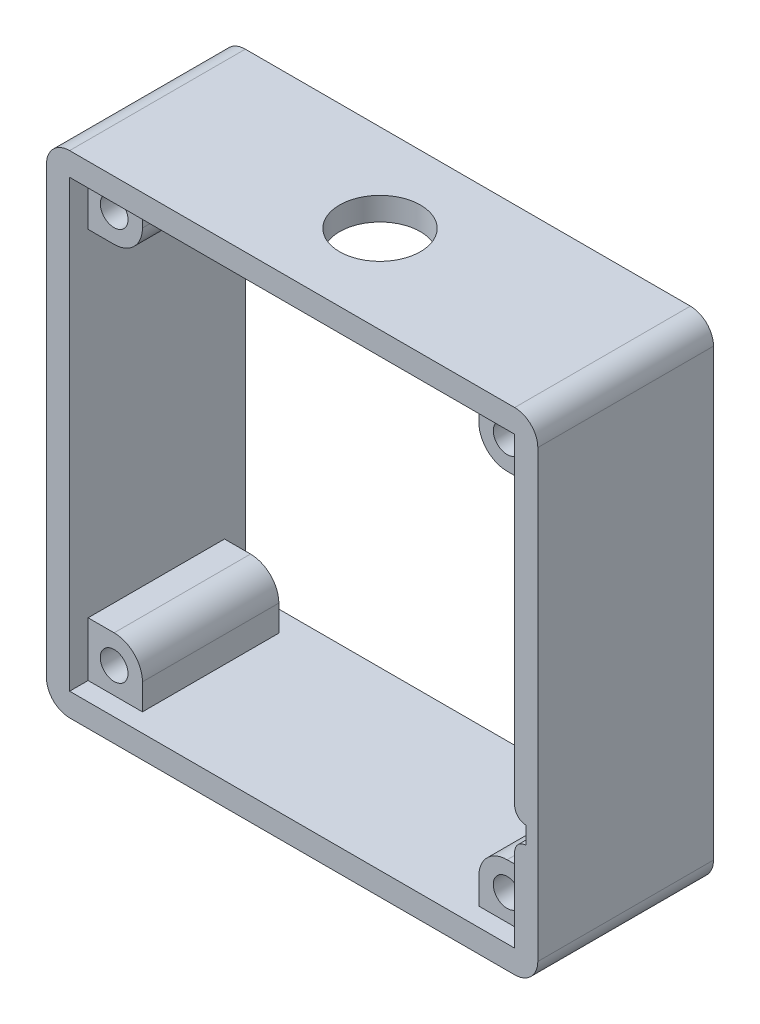
SolidWorks part; units mm, degrees
ref_plane "Front Plane" through (0, 0, 0) normal (0, 0, 1) x (1, 0, 0)
ref_plane "Top Plane" through (0, 0, 0) normal (0, 1, 0) x (1, 0, 0)
ref_plane "Right Plane" through (0, 0, 0) normal (1, 0, 0) x (0, 0, -1)
sketch "Sketch1" plane through (0, 0, 0) normal (0, 0, 1) x (1, 0, 0)
  line L0 (19.05, -19.05) -> (19.05, 19.05) construction
  line L5 (21.25, 21.25) -> (-21.25, 21.25)
  line L6 (-21.25, 21.25) -> (-21.25, -21.25)
  line L7 (-19.05, -19.05) -> (19.05, -19.05) construction
  line L8 (-19.05, 19.05) -> (-19.05, -19.05) construction
  line L9 (19.05, 19.05) -> (-19.05, 19.05) construction
  line L10 (19.05, -19.05) -> (19.05, 19.05) construction
  line L11 (-19.05, -19.05) -> (19.05, -19.05) construction
  line L12 (-19.05, 19.05) -> (-19.05, -19.05) construction
  line L13 (19.05, 19.05) -> (-19.05, 19.05) construction
  line L14 (19.25, -19.25) -> (19.25, 19.25)
  line L15 (19.25, 19.25) -> (-19.25, 19.25)
  line L16 (-19.25, 19.25) -> (-19.25, -19.25)
  line L17 (-19.25, -19.25) -> (19.25, -19.25)
  line L18 (-21.25, -21.25) -> (21.25, -21.25)
  line L19 (21.25, -21.25) -> (21.25, 21.25)
  point P336 (-1.13, 0.5101)
  dimension "D2" = 2
  dimension "D1" = 0.2
extrude "Boss-Extrude2" add sketch "Sketch1" against normal up to surface (15.2 mm away)
sketch "Sketch2" plane through (0, 0, -1.6) normal (0, 0, -1) x (-1, 0, 0)
  line L0 (17, -14.55) -> (19.25, -14.55)
  line L1 (19.25, 19.25) -> (19.25, -19.25) construction
  line L2 (14.55, -17) -> (14.55, -19.25)
  line L3 (19.25, -19.25) -> (-19.25, -19.25) construction
  line L4 (19.25, -19.25) -> (14.55, -19.25)
  line L5 (19.25, -14.55) -> (19.25, -19.25)
  line L6 (19.05, -19.05) -> (-19.05, -19.05) construction
  line L7 (0, 0) -> (-50000, 0) construction
  line L8 (0, 0) -> (0, 50000) construction
  line L9 (19.25, 14.55) -> (19.25, 19.25)
  line L10 (19.25, 19.25) -> (14.55, 19.25)
  line L11 (14.55, 17) -> (14.55, 19.25)
  line L12 (17, 14.55) -> (19.25, 14.55)
  line L13 (-19.25, -14.55) -> (-19.25, -19.25)
  line L14 (-19.25, -19.25) -> (-14.55, -19.25)
  line L15 (-14.55, -17) -> (-14.55, -19.25)
  line L16 (-17, -14.55) -> (-19.25, -14.55)
  line L17 (-17, 14.55) -> (-19.25, 14.55)
  line L18 (-14.55, 17) -> (-14.55, 19.25)
  line L19 (-19.25, 19.25) -> (-14.55, 19.25)
  line L20 (-19.25, 14.55) -> (-19.25, 19.25)
  circle A2 centre (17, -17) radius 1.2 construction
  circle A3 centre (17, -17) radius 1.2
  arc A4 (17, -14.55) -> (14.55, -17) centre (17, -17) ccw
  arc A5 (17, 14.55) -> (14.55, 17) centre (17, 17) cw
  circle A6 centre (17, 17) radius 1.2
  arc A7 (-17, -14.55) -> (-14.55, -17) centre (-17, -17) cw
  circle A8 centre (-17, -17) radius 1.2
  circle A9 centre (-17, 17) radius 1.2
  arc A10 (-17, 14.55) -> (-14.55, 17) centre (-17, 17) ccw
  dimension "D1" = 4.5
extrude "Boss-Extrude4" add sketch "Sketch2" along normal offset from surface (11.8 mm away) 0.2 up to face at (0, 0, 0)
fillet "Fillet1" radius 2 4 edges at (-21.25, 21.25, -7.6) (21.25, 21.25, -7.6) (21.25, -21.25, -7.6) (-21.25, -21.25, -7.6)
sketch "Sketch3" plane through (0, 0, 0) normal (0, 0, 1) x (1, 0, 0)
  line L0 (20.25, -11.05) -> (20.25, -9.55) construction
  line L1 (20.25, -11.05) -> (20.25, -9.55)
  line L2 (19.25, -8.55) -> (19.25, -12.05)
  arc A0 (19.25, -8.55) -> (20.25, -9.55) centre (20.25, -8.55) ccw construction
  arc A1 (20.25, -11.05) -> (19.25, -12.05) centre (20.25, -12.05) ccw construction
  arc A2 (19.25, -8.55) -> (20.25, -9.55) centre (20.25, -8.55) ccw
  arc A3 (20.25, -11.05) -> (19.25, -12.05) centre (20.25, -12.05) ccw
extrude "Cut-Extrude2" cut sketch "Sketch3" against normal blind 4
sketch "Sketch4" plane through (0, 21.25, 0) normal (0, 1, 0) x (1, 0, 0)
  line L0 (-19.25, 15.2) -> (-19.25, 0) construction
  line L1 (19.25, 0) -> (-19.25, 0) construction
  line L2 (19.25, 0) -> (19.25, 15.2) construction
  line L3 (19.25, 15.2) -> (-19.25, 15.2) construction
  line L4 (-19.25, 0) -> (-19.25, 15.2) construction
  line L5 (0, 15.2) -> (0, 0) construction
  line L6 (19.25, 7.6) -> (-19.25, 7.6) construction
  circle A0 centre (0, 7.6) radius 3.5
  point P6 (19.25, 0)
  point P7 (-19.25, 15.2)
  point P10 (0, 7.6)
  point P11 (-19.25, 5.8291)
  point P12 (-19.25, 15.2)
  point P102 (0, 7.6)
  dimension "D1" = 7
extrude "Cut-Extrude3" cut sketch "Sketch4" against normal up to next
